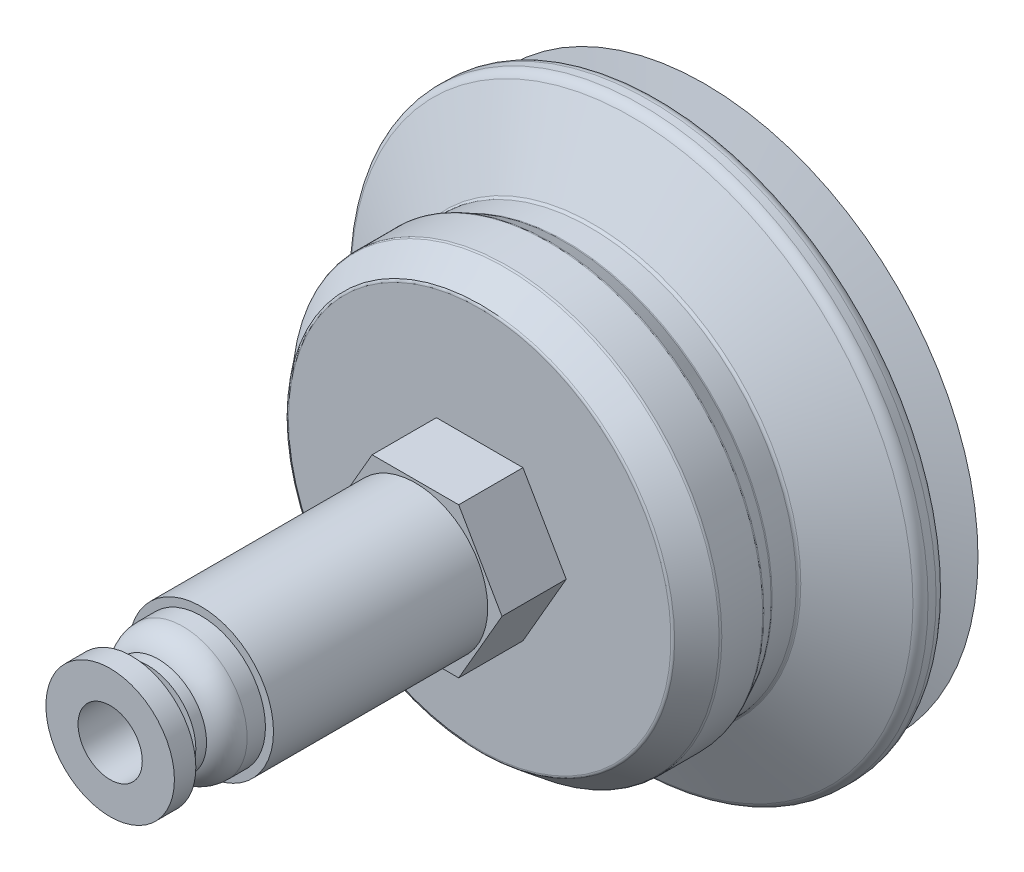
SolidWorks part; units mm, degrees
ref_plane "前视基准面" through (0, 0, 0) normal (0, 0, 1) x (1, 0, 0)
ref_plane "上视基准面" through (0, 0, 0) normal (0, 1, 0) x (1, 0, 0)
ref_plane "右视基准面" through (0, 0, 0) normal (1, 0, 0) x (0, 0, -1)
sketch "草图1" plane through (0, 0, 0) normal (0, 0, 1) x (1, 0, 0)
  line L0 (0, 0) -> (8.0829, 0) construction
  line L1 (8.0829, 0) -> (4.0415, 7)
  line L2 (4.0415, 7) -> (-4.0415, 7)
  line L3 (-4.0415, 7) -> (-8.0829, 0)
  line L4 (-8.0829, 0) -> (-4.0415, -7)
  line L5 (-4.0415, -7) -> (4.0415, -7)
  line L6 (4.0415, -7) -> (8.0829, 0)
  circle A0 centre (0, 0) radius 7 construction
  dimension "D1" = 14
extrude "凸台-拉伸1" add sketch "草图1" along normal blind 6
sketch "草图2" plane through (0, 0, 6) normal (0, 0, 1) x (1, 0, 0)
  circle A0 centre (0, 0) radius 6.75
  dimension "D1" = 13.5
extrude "凸台-拉伸2" add sketch "草图2" along normal blind 20
cosmetic thread "装饰螺纹线1" parameters "D2"=6.647
sketch "草图3" plane through (0, 0, 26) normal (0, 0, 1) x (1, 0, 0)
  circle A0 centre (0, 0) radius 6
  dimension "D1" = 12
extrude "凸台-拉伸3" add sketch "草图3" along normal blind 4
sketch "草图4" plane through (0, 0, 30) normal (0, 0, 1) x (1, 0, 0)
  circle A0 centre (0, 0) radius 4.5
  dimension "D1" = 9
extrude "凸台-拉伸4" add sketch "草图4" along normal blind 1
sketch "草图5" plane through (0, 0, 31) normal (0, 0, 1) x (1, 0, 0)
  circle A0 centre (0, 0) radius 3.5
  dimension "D1" = 7
extrude "凸台-拉伸5" add sketch "草图5" along normal blind 1.5
sketch "草图6" plane through (0, 0, 32.5) normal (0, 0, 1) x (1, 0, 0)
  circle A0 centre (0, 0) radius 6
  dimension "D1" = 12
extrude "凸台-拉伸6" add sketch "草图6" along normal blind 2
sketch "草图7" plane through (0, 0, 0) normal (0, 0, -1) x (-1, 0, 0)
  circle A0 centre (0, 0) radius 18
  dimension "D1" = 36
extrude "凸台-拉伸8" add sketch "草图7" along normal blind 2.5 draft 38.7 draft outward yes
sketch "草图9" plane through (0, 0, -2.5) normal (0, 0, -1) x (-1, 0, 0)
  circle A1 centre (0, 0) radius 20.0029
  circle A2 centre (0, 0) radius 20.0029
  dimension "D1" = 0
extrude "凸台-拉伸9" add sketch "草图9" along normal blind 4
sketch "草图10" plane through (0, 0, -6.5) normal (0, 0, -1) x (-1, 0, 0)
  circle A1 centre (0, 0) radius 20.0029
  circle A2 centre (0, 0) radius 20.0029
  dimension "D1" = 0
extrude "凸台-拉伸10" add sketch "草图10" along normal blind 1.5 draft 27
sketch "草图11" plane through (0, 0, -8) normal (0, 0, -1) x (-1, 0, 0)
  circle A1 centre (0, 0) radius 19.2386
  circle A2 centre (0, 0) radius 19.2386
  dimension "D1" = 0
extrude "凸台-拉伸11" add sketch "草图11" along normal blind 2.5
sketch "草图12" plane through (0, 0, -10.5) normal (0, 0, -1) x (-1, 0, 0)
  circle A1 centre (0, 0) radius 19.2386
  circle A2 centre (0, 0) radius 19.2386
  dimension "D1" = 0
extrude "凸台-拉伸12" add sketch "草图12" along normal blind 4 draft 62 draft outward yes
sketch "草图13" plane through (0, 0, -14.5) normal (0, 0, -1) x (-1, 0, 0)
  circle A1 centre (0, 0) radius 26.7615
  circle A2 centre (0, 0) radius 26.7615
  dimension "D1" = 0
extrude "凸台-拉伸13" add sketch "草图13" along normal blind 2
sketch "草图14" plane through (0, 0, -16.5) normal (0, 0, -1) x (-1, 0, 0)
  circle A1 centre (0, 0) radius 26.7615
  circle A2 centre (0, 0) radius 26.7615
  dimension "D1" = 0
extrude "凸台-拉伸14" add sketch "草图14" along normal blind 3 draft 66.1
sketch "草图15" plane through (0, 0, -19.5) normal (0, 0, -1) x (-1, 0, 0)
  circle A1 centre (0, 0) radius 19.9916
  circle A2 centre (0, 0) radius 19.9916
  dimension "D1" = 0
extrude "凸台-拉伸15" add sketch "草图15" along normal blind 1.5 draft 74.83 draft outward yes
fillet "圆角1" radius 1 2 edges at (-26.7615, 0, -16.5) (-26.7615, 0, -14.5)
fillet "圆角2" radius 0.3 1 edges at (-19.9916, 0, -19.5)
fillet "圆角3" radius 0.3 5 edges at (-18, 0, 0) (-20.0029, 0, -2.5) (-20.0029, 0, -6.5) (-19.2386, 0, -8) (-19.2386, 0, -10.5)
sketch "草图16" plane through (0, 0, -21) normal (0, 0, -1) x (-1, 0, 0)
  circle A0 centre (0, 0) radius 1.5
  dimension "D1" = 3
extrude "切除-拉伸2" cut sketch "草图16" against normal through all
sketch "草图17" plane through (0, 0, 34.5) normal (0, 0, 1) x (1, 0, 0)
  circle A0 centre (0, 0) radius 3
  dimension "D1" = 6
extrude "切除-拉伸3" cut sketch "草图17" against normal blind 8
fillet "圆角4" radius 2.5 1 edges at (6, 0, 30)
sketch "草图18" plane through (0, 0, -21) normal (0, 0, -1) x (-1, 0, 0)
  circle A0 centre (0, 0) radius 16.5
  dimension "D1" = 33
extrude "切除-拉伸4" cut sketch "草图18" against normal blind 6
sketch "草图19" plane through (0, 0, -15) normal (0, 0, -1) x (-1, 0, 0)
  circle A0 centre (0, 0) radius 10
  dimension "D1" = 20
extrude "切除-拉伸5" cut sketch "草图19" against normal blind 5
sketch "草图20" plane through (0, 0, -10) normal (0, 0, -1) x (-1, 0, 0)
  circle A0 centre (0, 0) radius 5.75
  circle A1 centre (0, 0) radius 1.5 construction
  circle A2 centre (0, 0) radius 1.5
  dimension "D1" = 11.5
extrude "凸台-拉伸16" add sketch "草图20" along normal blind 2
sketch "草图21" plane through (0, 0, -21) normal (0, 0, -1) x (-1, 0, 0)
  circle A0 centre (0, 0) radius 23.524
  circle A1 centre (0, 0) radius 25.524 construction
  dimension "D1" = 2
extrude "切除-拉伸6" cut sketch "草图21" against normal blind 3 draft 70
